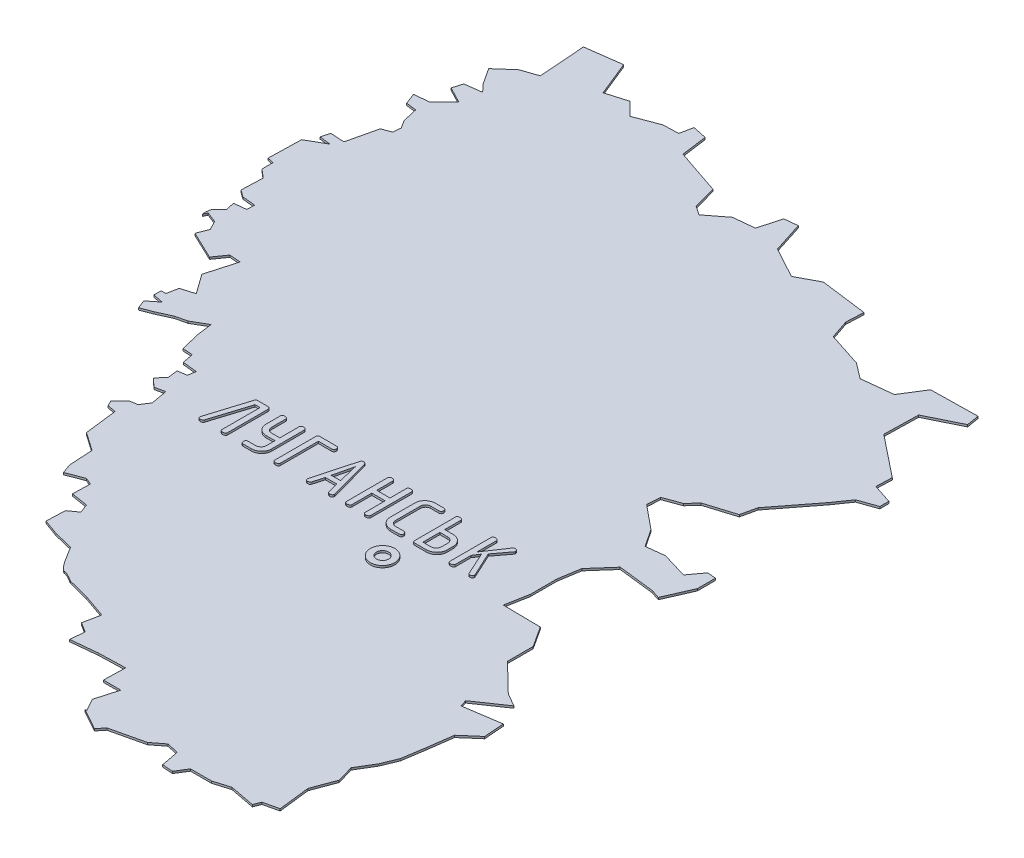
SolidWorks part; units mm, degrees
ref_plane "Спереди" through (0, 0, 0) normal (0, 0, 1) x (1, 0, 0)
ref_plane "Сверху" through (0, 0, 0) normal (0, 1, 0) x (1, 0, 0)
ref_plane "Справа" through (0, 0, 0) normal (1, 0, 0) x (0, 0, -1)
sketch "Эскиз1" plane through (0, 0, 0) normal (0, 1, 0) x (1, 0, 0)
  line B0 (5449.1941, 6425.1865) -> (5474.5179, 6386.2458)
  line B1 (5474.5179, 6386.2458) -> (5492.0286, 6367.4244)
  line B2 (5492.0286, 6367.4244) -> (5451.1448, 6362.225)
  line B3 (5451.1448, 6362.225) -> (5444.0125, 6338.2017)
  line B4 (5444.0125, 6338.2017) -> (5483.6009, 6317.4626)
  line B5 (5483.6009, 6317.4626) -> (5447.251, 6281.7604)
  line B6 (5447.251, 6281.7604) -> (5411.5843, 6278.5092)
  line B7 (5411.5843, 6278.5092) -> (5421.9526, 6251.2524)
  line B8 (5421.9526, 6251.2524) -> (5447.251, 6248.0139)
  line B9 (5447.251, 6248.0139) -> (5455.6685, 6211.664)
  line B10 (5455.6685, 6211.664) -> (5468.051, 6191.5599)
  line B11 (5468.051, 6191.5599) -> (5466.0825, 6172.7563)
  line B12 (5466.0825, 6172.7563) -> (5444.0125, 6164.2981)
  line B13 (5444.0125, 6164.2981) -> (5427.1418, 6092.2662)
  line B14 (5427.1418, 6092.2662) -> (5392.7781, 6094.2068)
  line B15 (5392.7781, 6094.2068) -> (5387.5813, 6073.4499)
  line B16 (5387.5813, 6073.4499) -> (5414.8126, 6070.2012)
  line B17 (5414.8126, 6070.2012) -> (5370.6751, 6044.8927)
  line B18 (5370.6751, 6044.8927) -> (5368.732, 5964.4305)
  line B19 (5368.732, 5964.4305) -> (5384.2996, 5961.1793)
  line B20 (5384.2996, 5961.1793) -> (5384.2996, 5933.9353)
  line B21 (5384.2996, 5933.9353) -> (5405.0895, 5916.4118)
  line B22 (5405.0895, 5916.4118) -> (5403.121, 5863.8567)
  line B23 (5403.121, 5863.8567) -> (5420.0019, 5851.5148)
  line B24 (5420.0019, 5851.5148) -> (5452.4402, 5848.2535)
  line B25 (5452.4402, 5848.2535) -> (5451.1448, 5829.4676)
  line B26 (5451.1448, 5829.4676) -> (5421.9526, 5826.2063)
  line B27 (5421.9526, 5826.2063) -> (5427.1418, 5805.4367)
  line B28 (5427.1418, 5805.4367) -> (5408.3356, 5786.6153)
  line B29 (5408.3356, 5786.6153) -> (5406.3671, 5771.6953)
  line B30 (5406.3671, 5771.6953) -> (5407.025, 5765.2158)
  line B31 (5407.025, 5765.2158) -> (5411.5843, 5774.9465)
  line B32 (5411.5843, 5774.9465) -> (5437.538, 5764.5681)
  line B33 (5437.538, 5764.5681) -> (5449.1941, 5742.5006)
  line B34 (5449.1941, 5742.5006) -> (5438.7979, 5715.2489)
  line B35 (5438.7979, 5715.2489) -> (5506.9384, 5682.7801)
  line B36 (5506.9384, 5682.7801) -> (5527.7385, 5712.0003)
  line B37 (5527.7385, 5712.0003) -> (5554.98, 5710.0572)
  line B38 (5554.98, 5710.0572) -> (5534.213, 5636.735)
  line B39 (5534.213, 5636.735) -> (5568.6198, 5588.6858)
  line B40 (5568.6198, 5588.6858) -> (5536.1815, 5578.9551)
  line B41 (5536.1815, 5578.9551) -> (5530.9668, 5551.6983)
  line B42 (5530.9668, 5551.6983) -> (5519.2676, 5551.6983)
  line B43 (5519.2676, 5551.6983) -> (5519.2676, 5534.1749)
  line B44 (5519.2676, 5534.1749) -> (5544.6016, 5528.9983)
  line B45 (5544.6016, 5528.9983) -> (5519.2676, 5508.8866)
  line B46 (5519.2676, 5508.8866) -> (5527.7385, 5488.112)
  line B47 (5527.7385, 5488.112) -> (5554.98, 5498.4955)
  line B48 (5554.98, 5498.4955) -> (5589.3513, 5514.0758)
  line B49 (5589.3513, 5514.0758) -> (5616.6004, 5520.563)
  line B50 (5616.6004, 5520.563) -> (5652.328, 5541.3326)
  line B51 (5652.328, 5541.3326) -> (5657.5096, 5501.7365)
  line B52 (5657.5096, 5501.7365) -> (5669.1809, 5455.6609)
  line B53 (5669.1809, 5455.6609) -> (5693.2119, 5454.3757)
  line B54 (5693.2119, 5454.3757) -> (5698.3909, 5427.1088)
  line B55 (5698.3909, 5427.1088) -> (5734.0678, 5423.2226)
  line B56 (5734.0678, 5423.2226) -> (5730.8293, 5404.3885)
  line B57 (5730.8293, 5404.3885) -> (5708.7872, 5401.1398)
  line B58 (5708.7872, 5401.1398) -> (5712.0333, 5377.1521)
  line B59 (5712.0333, 5377.1521) -> (5695.188, 5357.0149)
  line B60 (5695.188, 5357.0149) -> (5715.315, 5338.2062)
  line B61 (5715.315, 5338.2062) -> (5739.2646, 5343.3955)
  line B62 (5739.2646, 5343.3955) -> (5746.4147, 5302.5218)
  line B63 (5746.4147, 5302.5218) -> (5732.7902, 5281.7522)
  line B64 (5732.7902, 5281.7522) -> (5713.9586, 5278.5061)
  line B65 (5713.9586, 5278.5061) -> (5691.2612, 5256.4513)
  line B66 (5691.2612, 5256.4513) -> (5698.3909, 5242.8267)
  line B67 (5698.3909, 5242.8267) -> (5719.1732, 5238.9151)
  line B68 (5719.1732, 5238.9151) -> (5728.8862, 5159.1058)
  line B69 (5728.8862, 5159.1058) -> (5773.6562, 5127.9527)
  line B70 (5773.6562, 5127.9527) -> (5776.9277, 5070.2134)
  line B71 (5776.9277, 5070.2134) -> (5785.3631, 5046.1977)
  line B72 (5785.3631, 5046.1977) -> (5826.2291, 5061.773)
  line B73 (5826.2291, 5061.773) -> (5843.082, 5054.5975)
  line B74 (5843.082, 5054.5975) -> (5841.812, 5011.8035)
  line B75 (5841.812, 5011.8035) -> (5882.6781, 5005.3062)
  line B76 (5882.6781, 5005.3062) -> (5891.1134, 4983.2463)
  line B77 (5891.1134, 4983.2463) -> (5869.0612, 4967.6507)
  line B78 (5869.0612, 4967.6507) -> (5867.1104, 4921.6056)
  line B79 (5867.1104, 4921.6056) -> (5904.738, 4907.9506)
  line B80 (5904.738, 4907.9506) -> (5952.7973, 4896.2615)
  line B81 (6024.1561, 4824.2576) -> (6077.3589, 4810.633)
  line B82 (6077.3589, 4810.633) -> (6135.1312, 4790.5162)
  line B83 (6135.1312, 4790.5162) -> (6126.7035, 4748.977)
  line B84 (6126.7035, 4748.977) -> (6150.6989, 4734.0317)
  line B85 (6150.6989, 4734.0317) -> (6147.4782, 4699.0203)
  line B86 (6147.4782, 4699.0203) -> (6212.3269, 4705.4973)
  line B87 (6212.3269, 4705.4973) -> (6276.6092, 4707.448)
  line B88 (6276.6092, 4707.448) -> (6275.2707, 4654.2376)
  line B89 (6275.2707, 4654.2376) -> (6318.1128, 4654.2376)
  line B90 (6318.1128, 4654.2376) -> (6302.5376, 4599.7216)
  line B91 (6302.5376, 4599.7216) -> (6319.426, 4569.2238)
  line B92 (6319.426, 4569.2238) -> (6314.9124, 4569.2238)
  line B93 (6314.9124, 4569.2238) -> (6324.5975, 4564.0269)
  line B94 (6324.5975, 4564.0269) -> (6367.4752, 4539.9884)
  line B95 (6367.4752, 4539.9884) -> (6381.0744, 4556.9124)
  line B96 (6381.0744, 4556.9124) -> (6461.5619, 4575.7262)
  line B97 (6461.5619, 4575.7262) -> (6490.0962, 4597.7785)
  line B98 (6490.0962, 4597.7785) -> (6519.2885, 4591.2761)
  line B99 (6519.2885, 4591.2761) -> (6527.7492, 4547.1461)
  line B100 (6527.7492, 4547.1461) -> (6553.6877, 4545.2132)
  line B101 (6553.6877, 4545.2132) -> (6570.5584, 4572.4623)
  line B102 (6570.5584, 4572.4623) -> (6621.8359, 4572.4623)
  line B103 (6621.8359, 4572.4623) -> (6660.7919, 4584.1285)
  line B104 (6660.7919, 4584.1285) -> (6722.4046, 4572.4623)
  line B105 (6722.4046, 4572.4623) -> (6728.9248, 4589.333)
  line B106 (6728.9248, 4589.333) -> (6765.2494, 4597.7785)
  line B107 (6765.2494, 4597.7785) -> (6756.1562, 4675.0021)
  line B108 (6756.1562, 4675.0021) -> (6776.9664, 4730.7856)
  line B109 (6776.9664, 4730.7856) -> (6765.2494, 4771.71)
  line B110 (6765.2494, 4771.71) -> (6790.5554, 4813.8867)
  line B111 (6790.5554, 4813.8867) -> (6806.1307, 4851.4965)
  line B112 (6806.1307, 4851.4965) -> (6814.566, 4906.0176)
  line B113 (6814.566, 4906.0176) -> (6822.9683, 4967.6507)
  line B114 (6822.9683, 4967.6507) -> (6862.5898, 5002.0626)
  line B115 (6862.5898, 5002.0626) -> (6858.7061, 5051.3767)
  line B116 (6858.7061, 5051.3767) -> (6768.5031, 5037.7496)
  line B117 (6768.5031, 5037.7496) -> (6763.2986, 5054.5975)
  line B118 (6763.2986, 5054.5975) -> (6833.3899, 5102.639)
  line B119 (6833.3899, 5102.639) -> (6800.9338, 5121.4604)
  line B120 (6800.9338, 5121.4604) -> (6730.8425, 5189.601)
  line B121 (6730.8425, 5189.601) -> (6730.8425, 5252.5473)
  line B122 (6730.8425, 5252.5473) -> (6698.4042, 5302.5218)
  line B123 (6698.4042, 5302.5218) -> (6606.2784, 5303.8299)
  line B124 (6606.2784, 5303.8299) -> (6616.6467, 5360.2611)
  line B125 (6616.6467, 5360.2611) -> (6616.6467, 5425.1657)
  line B126 (6616.6467, 5425.1657) -> (6625.082, 5477.7259)
  line B127 (6625.082, 5477.7259) -> (6669.2018, 5527.6953)
  line B128 (6669.2018, 5527.6953) -> (6758.117, 5517.322)
  line B129 (6758.117, 5517.322) -> (6780.1693, 5510.182)
  line B130 (6780.1693, 5510.182) -> (6809.3514, 5577.0221)
  line B131 (6809.3514, 5577.0221) -> (6809.3514, 5621.147)
  line B132 (6809.3514, 5621.147) -> (6788.6047, 5623.0799)
  line B133 (6788.6047, 5623.0799) -> (6763.2986, 5588.6858)
  line B134 (6763.2986, 5588.6858) -> (6700.3371, 5607.5123)
  line B135 (6700.3371, 5607.5123) -> (6655.562, 5602.3154)
  line B136 (6655.562, 5602.3154) -> (6626.9997, 5645.1551)
  line B137 (6626.9997, 5645.1551) -> (6568.6076, 5693.1636)
  line B138 (6568.6076, 5693.1636) -> (6570.5584, 5725.6147)
  line B139 (6570.5584, 5725.6147) -> (6611.4574, 5740.5626)
  line B140 (6611.4574, 5740.5626) -> (6632.2397, 5763.26)
  line B141 (6632.2397, 5763.26) -> (6703.5655, 5785.3326)
  line B142 (6703.5655, 5785.3326) -> (6711.983, 5822.9729)
  line B143 (6711.983, 5822.9729) -> (6787.327, 5920.3107)
  line B144 (6787.327, 5920.3107) -> (6814.566, 5959.2388)
  line B145 (6814.566, 5959.2388) -> (6858.7061, 5974.8141)
  line B146 (6858.7061, 5974.8141) -> (6858.7061, 5996.8689)
  line B147 (6858.7061, 5996.8689) -> (6811.2945, 6012.4543)
  line B148 (6811.2945, 6012.4543) -> (6812.6153, 6051.3925)
  line B149 (6812.6153, 6051.3925) -> (6710.0856, 6133.1551)
  line B150 (6710.0856, 6133.1551) -> (6711.983, 6216.8786)
  line B151 (6711.983, 6216.8786) -> (6792.5061, 6256.4543)
  line B152 (6792.5061, 6256.4543) -> (6787.327, 6286.9572)
  line B153 (6787.327, 6286.9572) -> (6673.0956, 6285.0192)
  line B154 (6673.0956, 6285.0192) -> (6638.7167, 6230.4905)
  line B155 (6638.7167, 6230.4905) -> (6563.4337, 6222.0653)
  line B156 (6563.4337, 6222.0653) -> (6524.4955, 6251.2524)
  line B157 (6524.4955, 6251.2524) -> (6440.7517, 6278.5092)
  line B158 (6440.7517, 6278.5092) -> (6425.1764, 6324.6025)
  line B159 (6425.1764, 6324.6025) -> (6427.1449, 6367.4244)
  line B160 (6427.1449, 6367.4244) -> (6312.916, 6382.3444)
  line B161 (6312.916, 6382.3444) -> (6261.674, 6355.0952)
  line B162 (6261.674, 6355.0952) -> (6186.3732, 6395.9765)
  line B163 (6186.3732, 6395.9765) -> (6162.3804, 6471.2571)
  line B164 (6162.3804, 6471.2571) -> (6129.9674, 6468.0186)
  line B165 (6129.9674, 6468.0186) -> (6114.9967, 6413.4949)
  line B166 (6114.9967, 6413.4949) -> (6063.7268, 6408.3108)
  line B167 (6063.7268, 6408.3108) -> (6017.6715, 6372.6085)
  line B168 (6017.6715, 6372.6085) -> (5995.6217, 6387.5336)
  line B169 (5995.6217, 6387.5336) -> (5980.0617, 6444.013)
  line B170 (5980.0617, 6444.013) -> (5869.0612, 6481.6228)
  line B171 (5869.0612, 6481.6228) -> (5860.6004, 6544.5919)
  line B172 (5860.6004, 6544.5919) -> (5826.2291, 6551.7243)
  line B173 (5826.2291, 6551.7243) -> (5819.7775, 6520.5839)
  line B174 (5819.7775, 6520.5839) -> (5782.117, 6519.2859)
  line B175 (5782.117, 6519.2859) -> (5723.7249, 6497.2032)
  line B176 (5723.7249, 6497.2032) -> (5691.2612, 6529.0065)
  line B177 (5691.2612, 6529.0065) -> (5640.6466, 6514.084)
  line B178 (5640.6466, 6514.084) -> (5606.2397, 6599.0902)
  line B179 (5606.2397, 6599.0902) -> (5519.2676, 6587.4087)
  line B180 (5519.2676, 6587.4087) -> (5527.7385, 6473.1875)
  line B181 (5527.7385, 6473.1875) -> (5488.1323, 6459.568)
  line B182 (5488.1323, 6459.568) -> (5449.1941, 6425.1865)
  spline B183 degree 2 poles (5952.7973, 4896.2615) (5985.2077, 4839.8379) (5995.6217, 4837.8948) knots 0.435484 0.435484 0.435484 0.44086 0.44086 0.44086
  spline B184 degree 2 poles (5995.6217, 4837.8948) (6005.3245, 4836.574) (6024.1561, 4824.2576) knots 0.44086 0.44086 0.44086 0.446237 0.446237 0.446237
sketch_block_instance "Блок18-1"
sketch_block "Блок18"
extrude "Бобышка-Вытянуть7" add sketch "Эскиз1" along normal blind 5 contours B183 B184 B81 B82 B83 B84 B85 B86 B87 B88 B89 B90 B91 B92 B93 B94 B95 B96 B97 B98 B99 B100 B101 B102 B103 B104 B105 B106 B107 B108 B109 B110 B111 B112 B113 B114 B115 B116 B117 B118 B119 B120 region at (6152.5811, 0, -5613.9402)
sketch "Эскиз2" plane through (0, 0, 0) normal (0, 1, 0) x (1, 0, 0)
  line L0 (5832.6863, 5321.9381) -> (6662.6168, 5321.9381) construction
  circle A0 centre (6358.1007, 5256.0023) radius 15
  circle A1 centre (6358.1007, 5256.0023) radius 30
  text T0 "<b>ЛУГАНСЬК</b>" font "GOST Type AU" height 110
  dimension "D1" = 30
  dimension "D2" = 60
extrude "Бобышка-Вытянуть8" add sketch "Эскиз2" along normal blind 10
scale "Масштаб1" scale about centroid uniform scaling yes scale factor 0.05
